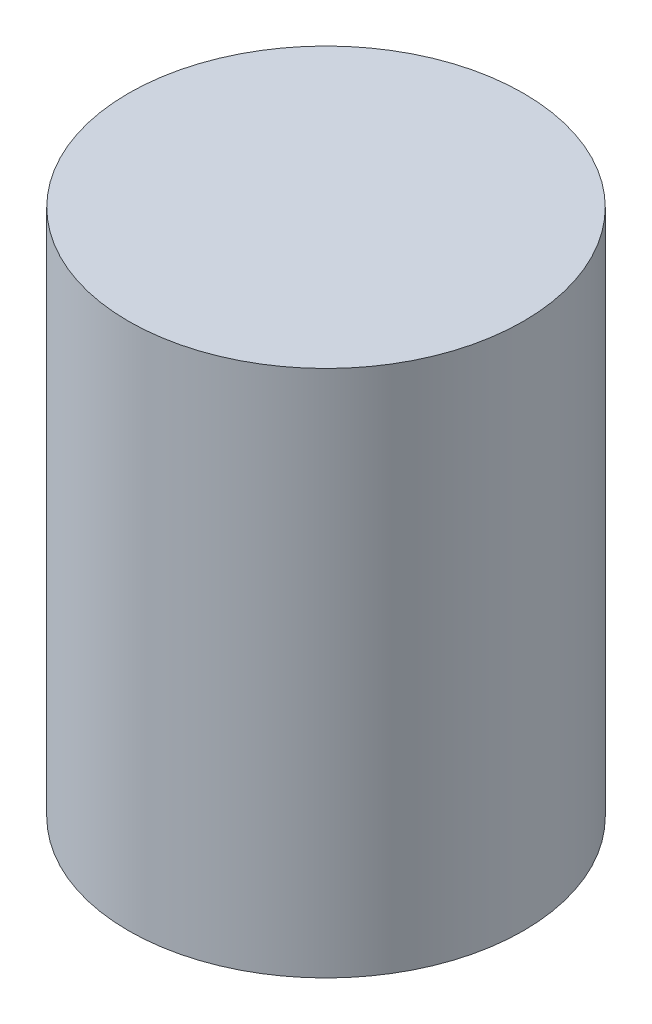
SolidWorks part; units mm, degrees
material "6061-T6 (SS)"
ref_plane "Piano frontale" through (0, 0, 0) normal (0, 0, 1) x (1, 0, 0)
ref_plane "Piano superiore" through (0, 0, 0) normal (0, 1, 0) x (1, 0, 0)
ref_plane "Piano destro" through (0, 0, 0) normal (1, 0, 0) x (0, 0, -1)
sketch "Schizzo1" plane through (0, 0, 0) normal (0, 0, 1) x (1, 0, 0)
  line L0 (0, 0) -> (0, 23.6846) construction
  line L1 (-14, 0) -> (-14, 38)
  line L2 (-14, 38) -> (0, 38)
  line L3 (0, 38) -> (0, 43)
  line L4 (0, 43) -> (-20, 43)
  line L5 (-20, 43) -> (-20, 0)
  line L6 (-20, 0) -> (-14, 0)
  line L7 (-20, 0) -> (-20, -10.4579)
  line L8 (-20, -10.4579) -> (-18, -10.4579)
  line L9 (-18, 0) -> (-18, -12) construction
  line L10 (-18, -10.4579) -> (-18, 0)
  line L11 (-18, 0) -> (-18, -12) construction
  dimension "D1" = 28
  dimension "D2" = 40
  dimension "D3" = 5
  dimension "D4" = 38
revolve "Rivoluzione1" add sketch "Schizzo1" angle 360 about L0 region at (-14.8659, 25.5549, 0) region at (-19, -5.229, 0)
